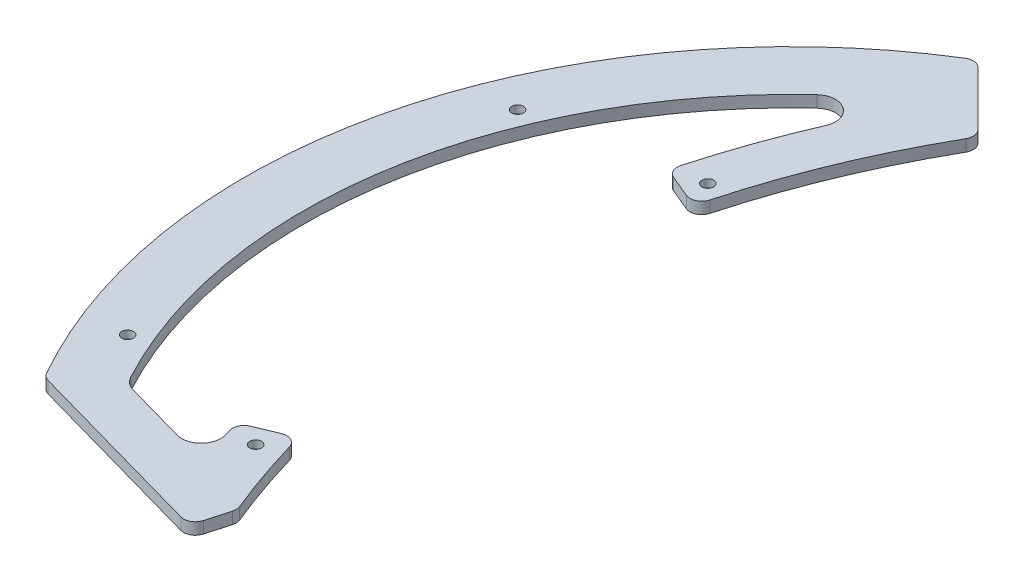
SolidWorks part; units mm, degrees
material "1060 Alloy"
ref_plane "Front Plane" through (0, 0, 0) normal (0, 0, 1) x (1, 0, 0)
ref_plane "Top Plane" through (0, 0, 0) normal (0, 1, 0) x (1, 0, 0)
ref_plane "Right Plane" through (0, 0, 0) normal (1, 0, 0) x (0, 0, -1)
sketch "Sketch1" plane through (0, 0, 0) normal (0, 1, 0) x (1, 0, 0)
  circle A0 centre (0, 0) radius 140
  dimension "D1" = 280
extrude "Boss-Extrude1" add sketch "Sketch1" along normal blind 3
sketch "Sketch17" plane through (0, 0, 0) normal (0, -1, 0) x (1, 0, 0)
  line L0 (-50, 90) -> (-121.2436, 70)
  line L1 (-50, 90) -> (50, 90)
  line L2 (-121.2436, 70) -> (-121.2436, 140)
  line L3 (-121.2436, 140) -> (121.2436, 140)
  line L4 (121.2436, 140) -> (121.2436, 70)
  line L5 (121.2436, 70) -> (50, 90)
  circle A0 centre (0, 0) radius 140 construction
  dimension "D1" = 90
  dimension "D2" = 50
  dimension "D3" = 50
  dimension "D4" = 70
extrude "Cut-Extrude1" cut sketch "Sketch17" against normal up to next
sketch "Sketch19" plane through (0, 3, 0) normal (0, 1, 0) x (1, 0, 0)
  line L0 (-68.5894, 68.5894) -> (68.5894, -68.5894) construction
  line L1 (97, 40.1787) -> (40.1787, 97) construction
  line L2 (40.1787, 97) -> (-40.1787, 97) construction
  line L3 (-40.1787, 97) -> (-97, 40.1787) construction
  line L4 (-97, 40.1787) -> (-97, -40.1787) construction
  line L5 (-97, -40.1787) -> (-40.1787, -97) construction
  line L6 (-40.1787, -97) -> (40.1787, -97) construction
  line L7 (40.1787, -97) -> (97, -40.1787) construction
  line L8 (97, -40.1787) -> (97, 40.1787) construction
  line L9 (68.5894, 68.5894) -> (-68.5894, -68.5894) construction
  circle A0 centre (-79.196, -57.9828) radius 1.5
  circle A1 centre (-79.196, 57.9828) radius 1.5
  circle A2 centre (79.196, 57.9828) radius 1.5
  circle A3 centre (79.196, -57.9828) radius 1.5
  circle A4 centre (0, 0) radius 97 construction
  circle A5 centre (-57.9828, 79.196) radius 1.5
  circle A6 centre (57.9828, 79.196) radius 1.5
  circle A7 centre (57.9828, -79.196) radius 1.5
  circle A8 centre (-57.9828, -79.196) radius 1.5
  dimension "D5" = 3
  dimension "D1" = 15
  dimension "D6" = 97
extrude "Cut-Extrude3" cut sketch "Sketch19" against normal up to next
sketch "Sketch25" plane through (0, 3, 0) normal (0, 1, 0) x (1, 0, 0)
  circle A0 centre (-120, 50) radius 1.5
  circle A1 centre (-120, -50) radius 1.5
  dimension "D1" = 3
  dimension "D2" = 50
  dimension "D3" = 50
  dimension "D4" = 120
extrude "Cut-Extrude10" cut sketch "Sketch25" against normal up to next
sketch "Sketch20" plane through (0, 3, 0) normal (0, 1, 0) x (1, 0, 0)
  line L0 (-72, 120.0666) -> (-50, 98.0666)
  line L1 (-50, 98.0666) -> (50, 98.0666)
  line L2 (50, 98.0666) -> (72, 120.0666)
  arc A1 (121.2436, -70) -> (-121.2436, -70) centre (0, 0) ccw construction
  dimension "D1" = 144
  dimension "D2" = 100
  dimension "D3" = 50
extrude "Cut-Extrude4" cut sketch "Sketch20" against normal up to next
fillet "Fillet2" radius 10 2 edges at (50, 1.5, -98.0666) (-50, 1.5, -98.0666)
sketch "Sketch23" plane through (0, 3, 0) normal (0, 1, 0) x (1, 0, 0)
  line L0 (-67.1106, -74.7122) -> (-73.1897, -96.3671)
  line L1 (-72, 120.0666) -> (-52.9289, 100.9956) construction
  line L2 (-121.2436, -70) -> (-50, -90) construction
  arc A0 (-54.9334, 103) -> (-67.1106, -74.7122) centre (117.6332, 1.902) ccw
  arc A3 (-67.1106, -74.7122) -> (-54.9334, -99.196) centre (117.6332, 1.902) ccw construction
  circle A4 centre (-57.9828, -79.196) radius 1.5 construction
  dimension "D1" = 103
  dimension "D2" = 20
  dimension "D3" = 200
  dimension "D4" = 90
  dimension "D5" = 10
extrude "Cut-Extrude8" cut sketch "Sketch23" against normal through all and the other way through all
sketch "Sketch24" plane through (0, 3, 0) normal (0, 1, 0) x (1, 0, 0)
  line L0 (-87.3571, 55.9666) -> (-76.1692, 51.3049)
  line L1 (-109.1428, -60.9331) -> (-82.3519, -68.4541)
  line L3 (-121.2436, -70) -> (-69.8389, -84.4307) construction
  line L4 (-86.4256, -55.5785) -> (-75.2633, -50.9275)
  line L5 (-120, 50) -> (0, 0) construction
  line L6 (0, 0) -> (-120, -50) construction
  line L7 (-76.1692, 51.3049) -> (-75.2633, -50.9275)
  arc A1 (-87.3571, 55.9666) -> (-67.4898, 105.2147) centre (117.6332, 1.902) cw
  arc A2 (-54.9334, 103) -> (-67.1106, -74.7122) centre (117.6332, 1.902) ccw construction
  arc A3 (-67.4898, 105.2147) -> (-109.1428, -60.9331) centre (0, 0) ccw
  circle A4 centre (-120, 50) radius 5 construction
  circle A5 centre (-120, -50) radius 5 construction
  arc A6 (-82.3519, -68.4541) -> (-86.4256, -55.5785) centre (117.6332, 1.902) cw
  circle A8 centre (-79.196, -57.9828) radius 1.5 construction
  circle A9 centre (-79.196, 57.9828) radius 1.5 construction
  dimension "D2" = 10
  dimension "D3" = 5
  dimension "D4" = 12
  dimension "D5" = 12
  dimension "D1" = 5
  dimension "D6" = 12
extrude "Cut-Extrude9" cut sketch "Sketch24" against normal up to next
fillet "Fillet4" radius 5 3 edges at (-82.3519, 1.5, 68.4541) (-109.1428, 1.5, 60.9331) (-67.4898, 1.5, -105.2147)
fillet "Fillet5" radius 3 9 edges at (-72, 1.5, -120.0666) (-67.1106, 1.5, 74.7122) (-69.8389, 1.5, 84.4307) (-121.2436, 1.5, 70) (-54.9334, 1.5, -103) (-86.4256, 1.5, 55.5785) (-75.2633, 1.5, 50.9275) (-87.3571, 1.5, -55.9666) (-76.1692, 1.5, -51.3049)
sketch "Sketch26" plane through (0, 0, 0) normal (0, -1, 0) x (1, 0, 0)
  circle A0 centre (-79.196, 57.9828) radius 3
  circle A1 centre (-120, 50) radius 3
  circle A2 centre (-120, -50) radius 3
  circle A3 centre (-79.196, -57.9828) radius 3
  dimension "D1" = 6
extrude "Cut-Extrude11" cut sketch "Sketch26" against normal blind 1
equation "\"D3@Sketch20\" = \"D2@Sketch20\" / 2"
